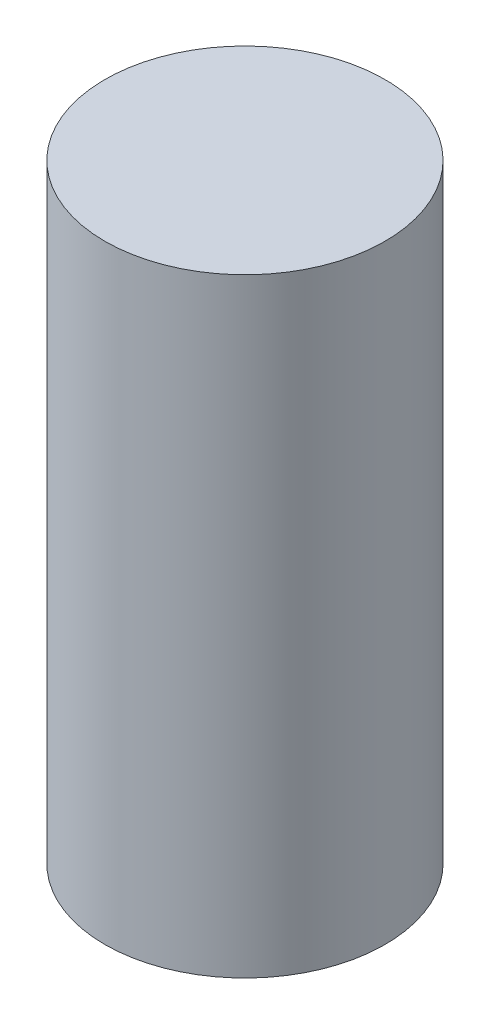
SolidWorks part; units mm, degrees
ref_plane "Plan de face" through (0, 0, 0) normal (0, 0, 1) x (1, 0, 0)
ref_plane "Plan de dessus" through (0, 0, 0) normal (0, 1, 0) x (1, 0, 0)
ref_plane "Plan de droite" through (0, 0, 0) normal (1, 0, 0) x (0, 0, -1)
sketch "Esquisse1" plane through (0, 0, 0) normal (0, 1, 0) x (1, 0, 0)
  circle A0 centre (0, 0) radius 73.61
  dimension "D1" = 147.22
extrude "Boss.-Extru.1" add sketch "Esquisse1" along normal blind 320
